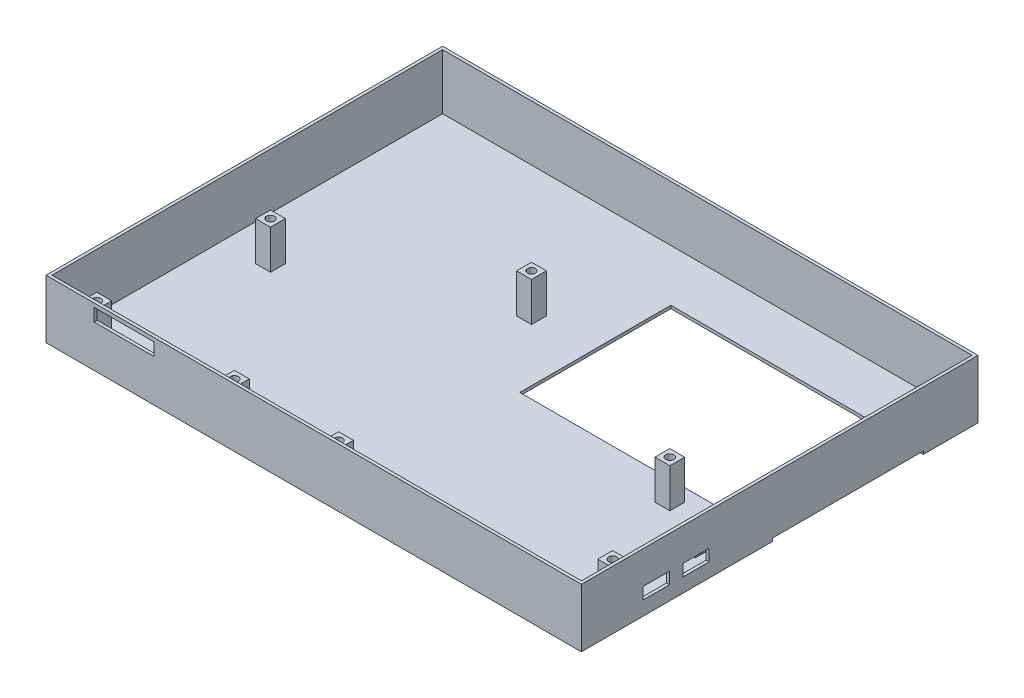
SolidWorks part; units mm, degrees
material "PLA"
ref_plane "Спереди" through (0, 0, 0) normal (0, 0, 1) x (1, 0, 0)
ref_plane "Сверху" through (0, 0, 0) normal (0, 1, 0) x (1, 0, 0)
ref_plane "Справа" through (0, 0, 0) normal (1, 0, 0) x (0, 0, -1)
sketch "Эскиз1" plane through (0, 0, 0) normal (0, 1, 0) x (1, 0, 0)
  line L1 (135, 100) -> (-135, 100)
  line L2 (135, 100) -> (135, -100)
  line L3 (135, -100) -> (-135, -100)
  line L4 (-135, 100) -> (-135, -100)
  line L5 (135, 100) -> (-135, -100) construction
  line L6 (135, -100) -> (-135, 100) construction
  point P0 (0, 0)
  dimension "D1" = 200
  dimension "D2" = 270
extrude "Бобышка-Вытянуть1" add sketch "Эскиз1" along normal blind 1.5
sketch "Эскиз2" plane through (0, 1.5, 0) normal (0, 1, 0) x (1, 0, 0)
  line L0 (133.5, 98.5) -> (-133.5, 98.5)
  line L1 (-133.5, 98.5) -> (-133.5, -98.5)
  line L2 (-133.5, -98.5) -> (-110.7, -98.5)
  line L3 (133.5, -98.5) -> (133.5, 98.5)
  line L4 (-135, 100) -> (-135, -100)
  line L5 (-135, -100) -> (135, -100)
  line L6 (135, -100) -> (135, 100)
  line L7 (135, 100) -> (-135, 100)
  line L8 (-135, 100) -> (-135, -100)
  line L9 (-135, -100) -> (-110.7, -100)
  line L10 (135, -100) -> (135, 100)
  line L11 (135, 100) -> (-135, 100)
  line L12 (-110.7, -98.5) -> (-110.7, -100)
  line L14 (-80.5, -98.5) -> (-80.5, -100)
  line L16 (-80.5, -98.5) -> (133.5, -98.5)
  line L17 (-80.5, -100) -> (135, -100)
  line L18 (-133.5, -98.5) -> (133.5, -98.5) construction
  line L20 (-135, -100) -> (135, -100) construction
  dimension "D3" = 24.3
  dimension "D4" = 54.5
  dimension "D1" = 0
  dimension "D2" = 1.5
extrude "Бобышка-Вытянуть2" add sketch "Эскиз2" along normal offset from surface (28 mm away) 7 offset beyond the face yes
sketch "Эскиз3" plane through (0, 1.5, 0) normal (0, 1, 0) x (1, 0, 0)
  line L1 (-110.7, -98.5) -> (-80.5, -98.5)
  line L2 (-110.7, -98.5) -> (-110.7, -100)
  line L3 (-110.7, -100) -> (-80.5, -100)
  line L4 (-80.5, -98.5) -> (-80.5, -100)
extrude "Бобышка-Вытянуть3" add sketch "Эскиз3" along normal blind 19.7
sketch "Эскиз4" plane through (-110.7, 0, 0) normal (1, 0, 0) x (0, 0, -1)
  line L0 (-100, 29.5) -> (-100, 21.2) construction
  line L1 (-98.5, 29.5) -> (-100, 29.5)
  line L2 (-98.5, 29.5) -> (-98.5, 27.6)
  line L3 (-98.5, 27.6) -> (-100, 27.6)
  line L4 (-100, 29.5) -> (-100, 27.6)
  dimension "D1" = 1.9
extrude "Бобышка-Вытянуть4" add sketch "Эскиз4" along normal up to surface (30.2 mm away) up to face at (-80.5, 25.35, 99.25)
sketch "Эскиз5" plane through (135, 0, 0) normal (1, 0, 0) x (0, 0, -1)
  line L0 (-100, 29.5) -> (-100, 0) construction
  line L1 (-55.55, 13) -> (-68.85, 13)
  line L2 (-55.55, 13) -> (-55.55, 7.1)
  line L3 (-55.55, 7.1) -> (-68.85, 7.1)
  line L4 (-68.85, 13) -> (-68.85, 7.1)
  line L5 (-55.55, 13) -> (-68.85, 7.1) construction
  line L6 (-55.55, 7.1) -> (-68.85, 13) construction
  line L7 (-35.55, 13) -> (-48.85, 13)
  line L8 (-35.55, 13) -> (-35.55, 7.1)
  line L9 (-35.55, 7.1) -> (-48.85, 7.1)
  line L10 (-48.85, 13) -> (-48.85, 7.1)
  line L11 (-35.55, 13) -> (-48.85, 7.1) construction
  line L12 (-35.55, 7.1) -> (-48.85, 13) construction
  line L13 (-100, 0) -> (100, 0) construction
  point P0 (-62.2, 10.05)
  point P5 (-42.2, 10.05)
  dimension "D1" = 13.3
  dimension "D2" = 5.9
  dimension "D3" = 6.7
  dimension "D4" = 31.15
  dimension "D5" = 13
extrude "Вырез-Вытянуть1" cut sketch "Эскиз5" against normal up to surface (1.5 mm away) up to face at (133.5, 15.5, 0)
sketch "Эскиз10" plane through (0, 1.5, 0) normal (0, 1, 0) x (1, 0, 0)
  line L0 (133.5, -14.85) -> (133.5, -98.5) construction
  line L1 (124.175, -24.225) -> (116.675, -24.225)
  line L2 (124.175, -24.225) -> (124.175, -31.725)
  line L3 (124.175, -31.725) -> (116.675, -31.725)
  line L4 (116.675, -24.225) -> (116.675, -31.725)
  line L5 (124.175, -24.225) -> (116.675, -31.725) construction
  line L6 (124.175, -31.725) -> (116.675, -24.225) construction
  line L7 (114.55, -56.3) -> (107.05, -56.3)
  line L8 (114.55, -56.3) -> (114.55, -63.8)
  line L9 (114.55, -63.8) -> (107.05, -63.8)
  line L10 (107.05, -56.3) -> (107.05, -63.8)
  line L11 (114.55, -56.3) -> (107.05, -63.8) construction
  line L12 (114.55, -63.8) -> (107.05, -56.3) construction
  line L13 (115.175, -89.275) -> (107.675, -89.275)
  line L14 (115.175, -89.275) -> (115.175, -96.775)
  line L15 (115.175, -96.775) -> (107.675, -96.775)
  line L16 (107.675, -89.275) -> (107.675, -96.775)
  line L17 (115.175, -89.275) -> (107.675, -96.775) construction
  line L18 (115.175, -96.775) -> (107.675, -89.275) construction
  line L19 (133.5, -98.5) -> (-133.5, -98.5) construction
  point P0 (120.425, -27.975)
  point P5 (110.8, -60.05)
  point P10 (111.425, -93.025)
  dimension "D1" = 13.075
  dimension "D2" = 70.525
  dimension "D3" = 22.7
  dimension "D4" = 38.45
  dimension "D5" = 22.075
  dimension "D6" = 5.475
  dimension "D7" = 7.5
extrude "Бобышка-Вытянуть6" add sketch "Эскиз10" along normal blind 6.9
sketch "Эскиз11" plane through (0, 1.5, 0) normal (0, 1, 0) x (1, 0, 0)
  line L1 (-46.7446, -85.75) -> (-54.2446, -85.75)
  line L2 (-46.7446, -85.75) -> (-46.7446, -93.25)
  line L3 (-46.7446, -93.25) -> (-54.2446, -93.25)
  line L4 (-54.2446, -85.75) -> (-54.2446, -93.25)
  line L5 (-46.7446, -85.75) -> (-54.2446, -93.25) construction
  line L6 (-46.7446, -93.25) -> (-54.2446, -85.75) construction
  line L7 (-19.0224, 28.8491) -> (-26.5224, 28.8491)
  line L8 (-19.0224, 28.8491) -> (-19.0224, 36.3491)
  line L9 (-19.0224, 36.3491) -> (-26.5224, 36.3491)
  line L10 (-26.5224, 28.8491) -> (-26.5224, 36.3491)
  line L11 (-19.0224, 28.8491) -> (-26.5224, 36.3491) construction
  line L12 (-19.0224, 36.3491) -> (-26.5224, 28.8491) construction
  line L13 (-115.5446, -93.8424) -> (-123.0446, -93.8424)
  line L14 (-115.5446, -93.8424) -> (-115.5446, -86.3424)
  line L15 (-115.5446, -86.3424) -> (-123.0446, -86.3424)
  line L16 (-123.0446, -93.8424) -> (-123.0446, -86.3424)
  line L17 (-115.5446, -93.8424) -> (-123.0446, -86.3424) construction
  line L18 (-115.5446, -86.3424) -> (-123.0446, -93.8424) construction
  line L19 (-107.65, -14.1324) -> (-115.15, -14.1324)
  line L20 (-107.65, -14.1324) -> (-107.65, -6.6324)
  line L21 (-107.65, -6.6324) -> (-115.15, -6.6324)
  line L22 (-115.15, -14.1324) -> (-115.15, -6.6324)
  line L23 (-107.65, -14.1324) -> (-115.15, -6.6324) construction
  line L24 (-107.65, -6.6324) -> (-115.15, -14.1324) construction
  line L25 (97.2279, -17.6196) -> (89.7279, -17.6196)
  line L26 (97.2279, -17.6196) -> (97.2279, -10.1196)
  line L27 (97.2279, -10.1196) -> (89.7279, -10.1196)
  line L28 (89.7279, -17.6196) -> (89.7279, -10.1196)
  line L29 (97.2279, -17.6196) -> (89.7279, -10.1196) construction
  line L30 (97.2279, -10.1196) -> (89.7279, -17.6196) construction
  line L31 (94.0554, -99.0196) -> (86.5554, -99.0196)
  line L32 (94.0554, -99.0196) -> (94.0554, -91.5196)
  line L33 (94.0554, -91.5196) -> (86.5554, -91.5196)
  line L34 (86.5554, -99.0196) -> (86.5554, -91.5196)
  line L35 (94.0554, -99.0196) -> (86.5554, -91.5196) construction
  line L36 (94.0554, -91.5196) -> (86.5554, -99.0196) construction
  line L37 (6.3554, -93.8285) -> (-1.1446, -93.8285)
  line L38 (6.3554, -93.8285) -> (6.3554, -86.3285)
  line L39 (6.3554, -86.3285) -> (-1.1446, -86.3285)
  line L40 (-1.1446, -93.8285) -> (-1.1446, -86.3285)
  line L41 (6.3554, -93.8285) -> (-1.1446, -86.3285) construction
  line L42 (6.3554, -86.3285) -> (-1.1446, -93.8285) construction
  line L44 (-133.5, 98.5) -> (133.5, 98.5) construction
  line L45 (-133.5, -98.5) -> (-133.5, 98.5) construction
  line L47 (133.5, -98.5) -> (-133.5, -98.5) construction
  line L48 (133.5, 98.5) -> (133.5, -98.5) construction
  point P0 (-50.4946, -89.5)
  point P5 (-22.7724, 32.5991)
  point P10 (-119.2946, -90.0924)
  point P15 (-111.4, -10.3824)
  point P20 (93.4779, -13.8696)
  point P25 (90.3054, -95.2696)
  point P30 (2.6054, -90.0785)
  dimension "D1" = 7.5
  dimension "D2" = 65.9009
  dimension "D3" = 110.7276
  dimension "D4" = 108.8824
  dimension "D5" = 22.1
  dimension "D6" = 8.4076
  dimension "D7" = 14.2054
  dimension "D8" = 8.4215
  dimension "D9" = 130.8946
  dimension "D10" = 9
  dimension "D11" = 83.0054
  dimension "D12" = 3.2304
  dimension "D13" = 43.1946
  dimension "D14" = 84.6304
  dimension "D15" = 40.0221
extrude "Бобышка-Вытянуть7" add sketch "Эскиз11" along normal blind 19.7
sketch "Эскиз12" plane through (0, 1.5, 0) normal (0, 1, 0) x (1, 0, 0)
  line L1 (135, 72.4) -> (7.7, 72.4)
  line L2 (135, 72.4) -> (135, -3.75)
  line L3 (135, -3.75) -> (7.7, -3.75)
  line L4 (7.7, 72.4) -> (7.7, -3.75)
  line L5 (-133.5, 98.5) -> (133.5, 98.5) construction
  line L6 (135, -100) -> (135, 100) construction
  dimension "D1" = 76.15
  dimension "D2" = 127.3
  dimension "D3" = 26.1
extrude "Вырез-Вытянуть2" cut sketch "Эскиз12" against normal through all
sketch "Эскиз14" plane through (0, 21.2, 0) normal (0, 1, 0) x (1, 0, 0)
  line L0 (-115.15, -6.6324) -> (-107.65, -14.1324) construction
  line L1 (-107.65, -6.6324) -> (-115.15, -14.1324) construction
  line L2 (-19.0224, 36.3491) -> (-26.5224, 28.8491) construction
  line L3 (-26.5224, 36.3491) -> (-19.0224, 28.8491) construction
  line L4 (-123.0446, -86.3424) -> (-115.5446, -93.8424) construction
  line L5 (-115.5446, -86.3424) -> (-123.0446, -93.8424) construction
  line L6 (-54.2446, -85.75) -> (-46.7446, -93.25) construction
  line L7 (-46.7446, -85.75) -> (-54.2446, -93.25) construction
  line L8 (-1.1446, -86.3285) -> (6.3554, -93.8285) construction
  line L9 (6.3554, -86.3285) -> (-1.1446, -93.8285) construction
  line L10 (94.0554, -91.5196) -> (86.5554, -99.0196) construction
  line L11 (94.0554, -91.5196) -> (86.5554, -91.5196) construction
  line L12 (94.0554, -91.5196) -> (94.0554, -99.0196) construction
  line L13 (94.0554, -99.0196) -> (86.5554, -99.0196) construction
  line L14 (86.5554, -91.5196) -> (86.5554, -99.0196) construction
  line L15 (94.0554, -99.0196) -> (86.5554, -91.5196) construction
  line L22 (97.2279, -10.1196) -> (89.7279, -17.6196) construction
  line L23 (97.2279, -17.6196) -> (89.7279, -10.1196) construction
  circle A0 centre (-22.7724, 32.5991) radius 2.05
  circle A1 centre (-111.4, -10.3824) radius 2.05
  circle A2 centre (-119.2946, -90.0924) radius 2.05
  circle A3 centre (-50.4946, -89.5) radius 2.05
  circle A4 centre (2.6054, -90.0785) radius 2.05
  circle A5 centre (90.3054, -95.2696) radius 2.05
  circle A6 centre (93.4779, -13.8696) radius 2.05
  dimension "D1" = 4.1
extrude "Вырез-Вытянуть4" cut sketch "Эскиз14" against normal blind 5
sketch "Эскиз15" plane through (0, 8.4, 0) normal (0, 1, 0) x (1, 0, 0)
  line L0 (124.175, -24.225) -> (116.675, -31.725) construction
  line L1 (116.675, -24.225) -> (124.175, -31.725) construction
  line L2 (107.05, -56.3) -> (114.55, -63.8) construction
  line L3 (114.55, -56.3) -> (107.05, -63.8) construction
  line L4 (107.675, -89.275) -> (115.175, -96.775) construction
  line L5 (115.175, -89.275) -> (107.675, -96.775) construction
  circle A0 centre (111.425, -93.025) radius 2.05
  circle A1 centre (110.8, -60.05) radius 2.05
  circle A2 centre (120.425, -27.975) radius 2.05
  dimension "D1" = 4.1
extrude "Вырез-Вытянуть5" cut sketch "Эскиз15" against normal blind 5
